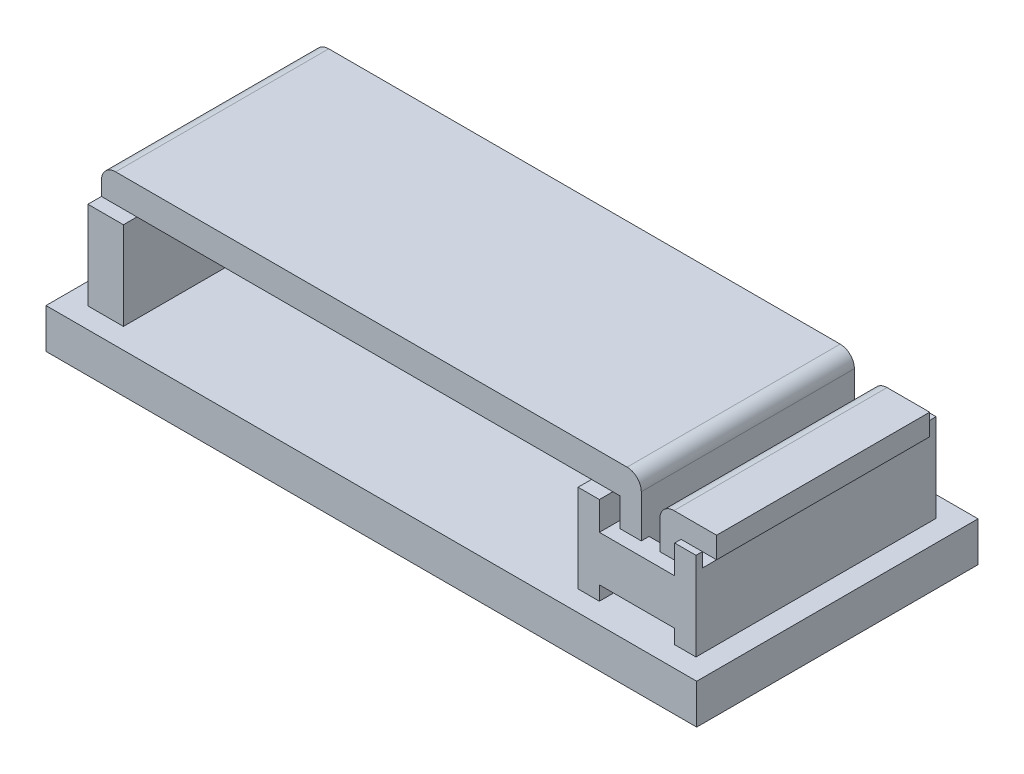
SolidWorks part; units mm, degrees
ref_plane "Front Plane" through (0, 0, 0) normal (0, 0, 1) x (1, 0, 0)
ref_plane "Top Plane" through (0, 0, 0) normal (0, 1, 0) x (1, 0, 0)
ref_plane "Right Plane" through (0, 0, 0) normal (1, 0, 0) x (0, 0, -1)
sketch "Base Outline" plane through (0, 0, 0) normal (0, 1, 0) x (1, 0, 0)
  line L1 (-22.9, -9.9) -> (22.9, -9.9)
  line L2 (-22.9, -9.9) -> (-22.9, 9.9)
  line L3 (-22.9, 9.9) -> (22.9, 9.9)
  line L4 (22.9, -9.9) -> (22.9, 9.9)
  point P4 (0, 9.9)
  point P6 (22.9, 0)
  dimension "Overall_Length" = 45.8
  dimension "Overall_Width" = 19.8
extrude "Clamp Base" add sketch "Base Outline" along normal blind 2.8
sketch "Hinge and Latch Outline" plane through (0, 0, 0) normal (0, 0, 1) x (1, 0, 0)
  line L0 (-22.9, 2.8) -> (22.9, 2.8) construction
  line L1 (-22.9, 2.8) -> (22.9, 2.8) construction
  line L2 (-21.4, 2.8) -> (-21.4, 9)
  line L3 (-21.4, 9) -> (-18.9, 9)
  line L4 (-18.9, 9) -> (-18.9, 2.8)
  line L5 (-21.4, 2.8) -> (-18.9, 2.8)
  line L6 (13.1, 2.8) -> (13.1, 9)
  line L7 (13.1, 2.8) -> (21.4, 2.8)
  line L9 (21.4, 2.8) -> (21.4, 9)
  line L10 (21.4, 9) -> (13.1, 9)
  point P2 (-21.4, 2.8)
  point P3 (21.4, 2.8)
  point P6 (-18.9, 2.8)
  point P10 (13.1, 2.8)
  dimension "Cable_Height" = 6.2
  dimension "Maximum_Cable_Width" = 32
extrude "Clip Hinge and Latch" add sketch "Hinge and Latch Outline" along normal mid plane 16.9
sketch "Side Cuts Outline" plane through (0, 0, 8.45) normal (0, 0, 1) x (1, 0, 0)
  line L0 (21.4, 9) -> (13.1, 9) construction
  line L1 (13.1, 2.8) -> (21.4, 2.8) construction
  line L3 (14.6, 9) -> (19.9, 9)
  line L4 (14.6, 9) -> (14.6, 7)
  line L5 (14.6, 7) -> (19.9, 7)
  line L6 (19.9, 9) -> (19.9, 7)
  line L7 (14.6, 2.8) -> (19.9, 2.8)
  line L8 (14.6, 2.8) -> (14.6, 3.8)
  line L9 (14.6, 3.8) -> (19.9, 3.8)
  line L10 (19.9, 2.8) -> (19.9, 3.8)
  point P0 (17.25, 9)
  point P1 (17.25, 2.8)
  point P14 (17.25, 7)
  point P15 (17.25, 3.8)
  dimension "Side_Cut_One_Depth" = 2
  dimension "Side_Cut_Two_Depth" = 1
  dimension "Side_Cut_Width" = 5.3
extrude "Latch Sides Cut" cut sketch "Side Cuts Outline" against normal up to next
sketch "Through Cut Outline" plane through (0, 7, 0) normal (0, 1, 0) x (1, 0, 0)
  line L2 (14.6, 8.45) -> (14.6, -8.45) construction
  line L3 (19.9, 8.45) -> (19.9, -8.45) construction
  line L5 (14.6, 6.95) -> (19.9, 6.95)
  line L6 (14.6, 6.95) -> (14.6, -6.95)
  line L7 (14.6, -6.95) -> (19.9, -6.95)
  line L8 (19.9, 6.95) -> (19.9, -6.95)
  point P0 (14.6, 6.95)
  point P1 (19.9, -6.95)
extrude "Latch Through Cut" cut sketch "Through Cut Outline" against normal up to next
sketch "Front Cut Outline" plane through (21.4, 0, 0) normal (1, 0, 0) x (0, 0, -1)
  line L1 (-8.45, 9) -> (8.45, 9) construction
  line L2 (-8, 9) -> (8, 9)
  line L3 (-8, 9) -> (-8, 8)
  line L4 (-8, 8) -> (8, 8)
  line L5 (8, 9) -> (8, 8)
  point P0 (0, 9)
  point P7 (0, 9)
  point P8 (0, 8)
  dimension "Front_Cut_Depth" = 1
  dimension "Front Cut Width" = 16
extrude "Latch Front Cut" cut sketch "Front Cut Outline" against normal up to next
sketch "Mid-Point Latch Back Point" plane through (0, 9, 0) normal (0, 1, 0) x (1, 0, 0)
  line L0 (14.6, 8.45) -> (14.6, -8.45) construction
  line L1 (14.6, 8.45) -> (14.6, -8.45) construction
  point P2 (14.6, 0)
sketch "Mid-Point Latch Front Point" plane through (0, 8, 0) normal (0, 1, 0) x (1, 0, 0)
  line L0 (19.9, 8) -> (19.9, -8) construction
  line L1 (19.9, 8) -> (19.9, -8) construction
  point P2 (19.9, 0)
sketch "Clamp Outline" plane through (0, 0, 0) normal (0, 0, 1) x (1, 0, 0)
  line L0 (-22.9, 2.8) -> (22.9, 2.8) construction
  line L1 (-21.4, 9) -> (15.1, 9)
  line L2 (-21.4, 9) -> (-21.4, 11)
  line L3 (-21.4, 11) -> (16.6, 11)
  line L4 (15.1, 9) -> (15.1, 3.3)
  line L5 (15.1, 3.3) -> (19.4, 3.3)
  line L6 (-22.9, 2.8) -> (22.9, 2.8) construction
  line L8 (16.6, 11) -> (16.6, 4.8)
  line L9 (17.9, 10) -> (21.9, 10)
  line L12 (17.9, 10) -> (17.9, 4.8)
  line L14 (19.4, 8.5) -> (19.4, 3.3)
  line L15 (21.9, 8.5) -> (21.9, 10)
  line L16 (16.6, 4.8) -> (17.9, 4.8)
  line L17 (21.9, 8.5) -> (19.4, 8.5)
  point P21 (21.9, 8.5)
  dimension "D1" = 0.5
  dimension "D2" = 0.5
  dimension "D3" = 0.5
  dimension "D7" = 0.5
  dimension "Finger_Pad_Width" = 4
  dimension "Clamp_Thickness" = 2
extrude "Clamp" add sketch "Clamp Outline" along normal mid plane 15
fillet "Clamp Fillets" radius 1 6 edges at (19.4, 8.5, 0) (17.9, 10, 0) (16.6, 11, 0) (-21.4, 11, 0) (19.4, 3.3, 0) (15.1, 3.3, 0)
sketch3d "Centre Lines Through Clips"
  line L0 (-18.9, 5.9, 8.45) -> (13.1, 5.9, 8.45) construction
  line L1 (13.1, 5.9, -8.45) -> (-18.9, 5.9, -8.45) construction
  line L4 (13.1, 9, 8.45) -> (13.1, 2.8, 8.45) construction
  line L5 (13.1, 9, -8.45) -> (13.1, 2.8, -8.45) construction
  line L7 (-18.9, 2.8, 8.45) -> (-18.9, 9, 8.45) construction
  line L8 (-2.9, 5.9, 8.15) -> (-2.9, 5.9, -8.15) construction
  line L9 (-18.9, 2.8, -8.45) -> (-18.9, 9, -8.45) construction
  line L10 (-18.9, 2.8, 8.45) -> (-18.9, 9, 8.45) construction
  line L11 (-18.9, 2.8, -8.45) -> (-18.9, 9, -8.45) construction
  point P2 (-3, 5.9, 8.45)
  point P5 (-2.9, 5.9, -8.45)
  point P16 (-2.9, 5.9, 0)
ref_axis "Ribbon Cable Axis" through (-2.9, 5.9, 8.15) along (0, 0, -1)
other "RPoint1"
